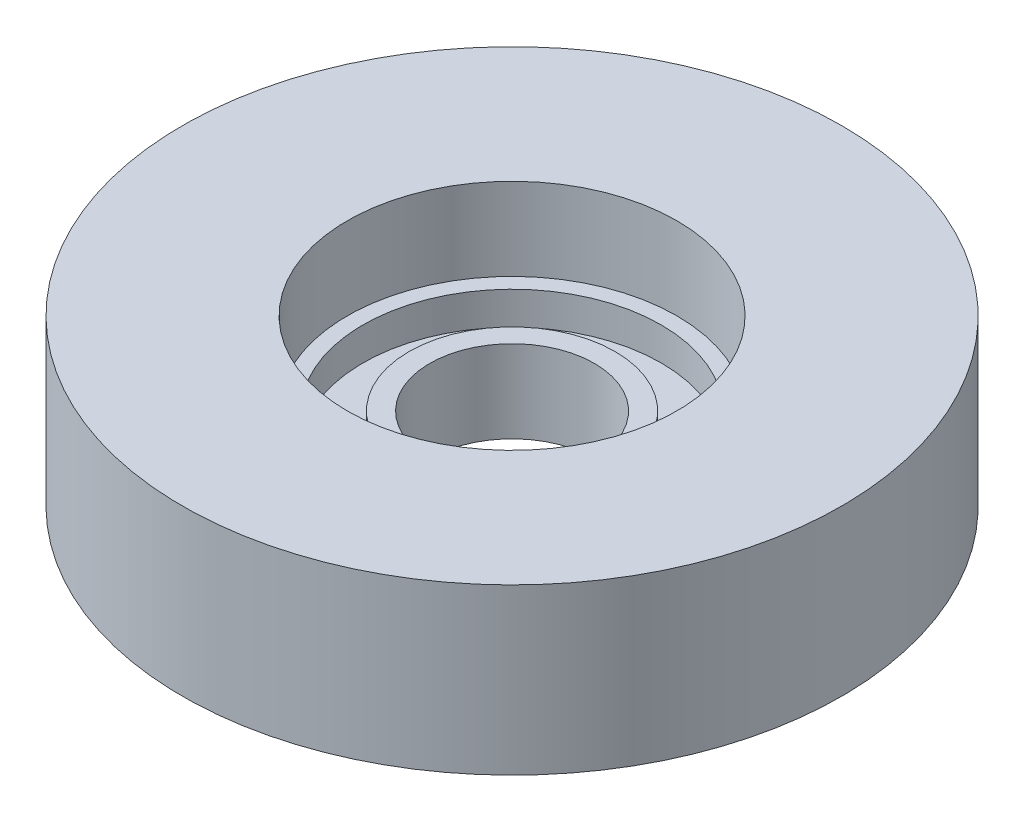
SolidWorks part; units mm, degrees
ref_plane "Front Plane" through (0, 0, 0) normal (0, 0, 1) x (1, 0, 0)
ref_plane "Top Plane" through (0, 0, 0) normal (0, 1, 0) x (1, 0, 0)
ref_plane "Right Plane" through (0, 0, 0) normal (1, 0, 0) x (0, 0, -1)
sketch "Sketch1" plane through (0, 0, 0) normal (0, 0, 1) x (1, 0, 0)
  line L0 (-6.35, 0) -> (-6.35, 6.35)
  line L1 (-11.4935, 6.35) -> (-12.7, 6.35)
  line L2 (-12.7, 6.35) -> (-12.7, 12.7)
  line L3 (-12.7, 12.7) -> (-25.4, 12.7)
  line L4 (-25.4, 12.7) -> (-25.4, 0)
  line L5 (-20.2565, 0) -> (-6.35, 0)
  line L6 (0, 0) -> (0, 10.2706) construction
  line L7 (-11.4935, 6.35) -> (-11.4935, 3.81)
  line L8 (-11.4935, 3.81) -> (-7.9375, 3.81)
  line L9 (-7.9375, 3.81) -> (-7.9375, 6.35)
  line L10 (-7.9375, 6.35) -> (-6.35, 6.35)
  line L11 (-25.4, 0) -> (-23.8125, 0)
  line L12 (-23.8125, 0) -> (-23.8125, 2.54)
  line L13 (-23.8125, 2.54) -> (-20.2565, 2.54)
  line L14 (-20.2565, 2.54) -> (-20.2565, 0)
  point P14 (-23.8526, 0)
  dimension "D1" = 6.35
  dimension "D2" = 2.54
  dimension "D3" = 6.35
  dimension "D4" = 6.35
  dimension "D5" = 25.4
  dimension "D6" = 3.556
  dimension "D7" = 6.35
  dimension "D8" = 1.5875
  dimension "D9" = 1.5875
  dimension "D10" = 2.54
  dimension "D11" = 3.556
revolve "Revolve1" add sketch "Sketch1" angle 360 about L6
